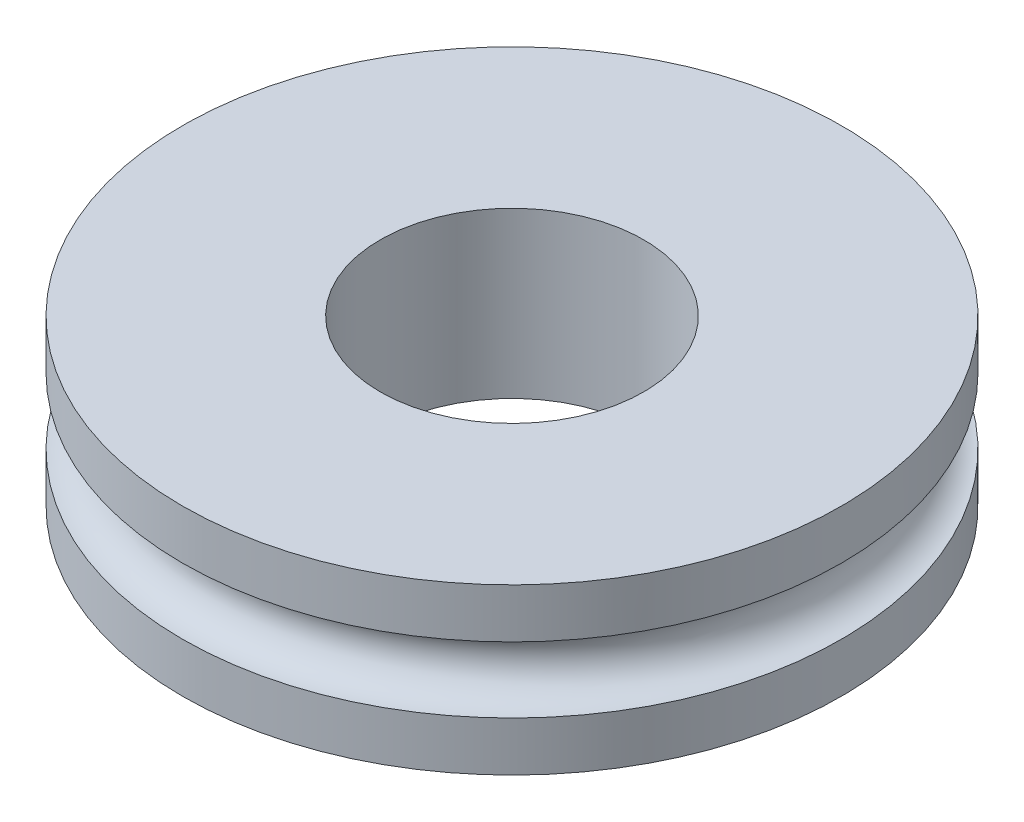
SolidWorks part; units mm, degrees
ref_plane "Plan de face" through (0, 0, 0) normal (0, 0, 1) x (1, 0, 0)
ref_plane "Plan de dessus" through (0, 0, 0) normal (0, 1, 0) x (1, 0, 0)
ref_plane "Plan de droite" through (0, 0, 0) normal (1, 0, 0) x (0, 0, -1)
sketch "Esquisse1" plane through (0, 0, 0) normal (0, 1, 0) x (1, 0, 0)
  circle A0 centre (0, 0) radius 5
  circle A1 centre (0, 0) radius 2
  dimension "D1" = 10
  dimension "D2" = 4
extrude "Boss.-Extru.1" add sketch "Esquisse1" along normal blind 1.25 and the other way blind 1.25
sketch "Esquisse2" plane through (0, 0, 0) normal (0, 0, 1) x (1, 0, 0)
  line L0 (0, 0) -> (5, 0) construction
  line L1 (5, -1.25) -> (5, 1.25) construction
  line L2 (0, -3.424) -> (0, 3.9562) construction
  circle A0 centre (5, 0) radius 0.5
  dimension "D1" = 1
revolve "Enlèvement de matière-Révolution1" cut sketch "Esquisse2" angle 360 about L2
